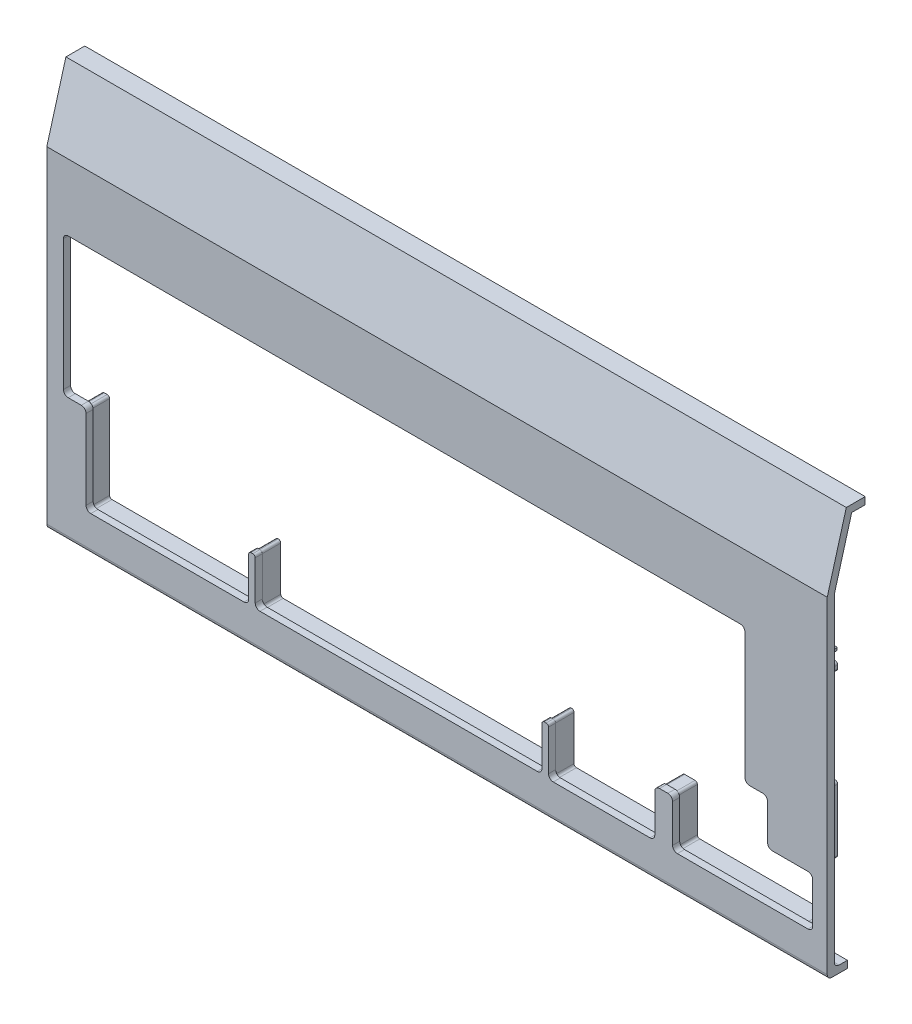
SolidWorks part; units mm, degrees
material "PET"
ref_plane "Front Plane" through (0, 0, 0) normal (0, 0, 1) x (1, 0, 0)
ref_plane "Top Plane" through (0, 0, 0) normal (0, 1, 0) x (1, 0, 0)
ref_plane "Right Plane" through (0, 0, 0) normal (1, 0, 0) x (0, 0, -1)
sketch "topprofile" plane through (853.0071, 0, 0) normal (1, 0, 0) x (0, 0, -1)
  line L0 (-0.0086, 1025.776) -> (-7.9776, 1025.776)
  line L2 (-16.0411, 996.9805) -> (-16.0411, 864.9805)
  line L8 (-13.0411, 864.9805) -> (-13.0411, 996.5684)
  line L10 (-5.7023, 1022.776) -> (-0.0086, 1022.776)
  line L11 (-0.0086, 1022.776) -> (-0.0086, 1025.776)
  line L13 (-16.0411, 996.9805) -> (-7.9776, 1025.776)
  line L15 (-5.7023, 1022.776) -> (-13.0411, 996.5684)
  line L16 (-13.0411, 864.9805) -> (-13.0411, 861.9953)
  line L17 (-11.0411, 859.9953) -> (-7.5187, 859.9953)
  line L18 (-16.0411, 864.9805) -> (-16.0411, 858.9953)
  line L19 (-14.0411, 856.9953) -> (-7.5187, 856.9953)
  line L20 (-7.5187, 859.9953) -> (-7.5187, 856.9953)
  arc A5 (-11.0411, 859.9953) -> (-13.0411, 861.9953) centre (-11.0411, 861.9953) cw
  arc A6 (-14.0411, 856.9953) -> (-16.0411, 858.9953) centre (-14.0411, 858.9953) cw
  dimension "D1" = 3
  dimension "D2" = 3
  dimension "D4" = 3
  dimension "D7" = 2
  dimension "D3" = 3
  dimension "D5" = 28.7954
  dimension "D6" = 132
extrude "faceplate" add sketch "topprofile" against normal up to surface (329.5 mm away)
sketch "keyboardcutout" plane through (0, 0, 16.0411) normal (0, 0, 1) x (1, 0, 0)
  line L0 (533.6471, 967.3544) -> (518.4377, 967.3544) construction
  line L1 (818.2971, 966.8544) -> (818.2971, 913.7044)
  line L2 (532.0471, 965.7544) -> (532.0471, 1029.3742) construction
  line L3 (530.5471, 966.8544) -> (530.5471, 911.7042)
  line L4 (532.5471, 968.8544) -> (816.2971, 968.8544)
  line L5 (816.7971, 965.7544) -> (816.7971, 984.5183) construction
  line L6 (824.7221, 910.2044) -> (842.7277, 910.2044) construction
  line L7 (826.3221, 908.6044) -> (826.3221, 926.0593) construction
  line L8 (843.7721, 891.1544) -> (863.4102, 891.1544) construction
  line L9 (820.2971, 911.7044) -> (825.8221, 911.7044)
  line L10 (827.8221, 909.7044) -> (827.8221, 894.6544)
  line L11 (829.8221, 892.6544) -> (844.8721, 892.6544)
  line L12 (845.3721, 889.5544) -> (845.3721, 899.3124) construction
  line L13 (846.8721, 890.6544) -> (846.8721, 873.6044)
  line L14 (843.7721, 873.1044) -> (861.095, 873.1044) construction
  line L15 (778.1971, 871.6044) -> (737.3346, 871.6044)
  line L16 (541.5721, 874.7044) -> (541.5721, 863.5167) construction
  line L17 (540.0721, 907.7042) -> (540.0721, 874.1044)
  line L18 (533.6471, 911.2042) -> (518.4377, 911.2042) construction
  line L19 (532.5471, 909.7042) -> (538.0721, 909.7042)
  line L20 (778.6971, 874.7044) -> (778.6971, 855.2363) construction
  line L21 (789.2221, 874.7044) -> (789.2221, 854.6734) construction
  line L22 (780.1971, 889.6544) -> (780.1971, 873.6044)
  line L23 (787.7221, 889.6544) -> (787.7221, 873.6044)
  line L24 (782.1971, 891.6544) -> (785.7221, 891.6544)
  line L25 (844.8721, 871.6044) -> (789.7221, 871.6044)
  line L26 (734.3346, 891.6544) -> (733.5721, 891.6544)
  line L27 (732.5721, 890.6544) -> (732.5721, 874.1044)
  line L28 (735.3346, 890.6544) -> (735.3346, 873.6044)
  line L29 (731.0721, 874.7044) -> (731.0721, 860.4434) construction
  line L30 (736.8346, 874.7044) -> (736.8346, 860.8815) construction
  line L31 (606.7471, 872.1044) -> (542.0721, 872.1044)
  line L32 (607.2471, 874.7044) -> (607.2471, 868.5767) construction
  line L33 (609.7471, 891.6544) -> (610.5096, 891.6544)
  line L34 (608.7471, 890.6544) -> (608.7471, 874.1044)
  line L36 (611.5096, 890.6544) -> (611.5096, 874.1044)
  line L37 (613.0096, 874.7044) -> (613.0096, 868.2785) construction
  line L38 (730.5721, 872.1044) -> (613.5096, 872.1044)
  arc A0 (530.5471, 911.7042) -> (532.5471, 909.7042) centre (532.5471, 911.7042) ccw
  arc A1 (540.0721, 907.7042) -> (538.0721, 909.7042) centre (538.0721, 907.7042) ccw
  arc A2 (540.0721, 874.1044) -> (542.0721, 872.1044) centre (542.0721, 874.1044) ccw
  arc A3 (606.7471, 872.1044) -> (608.7471, 874.1044) centre (606.7471, 874.1044) ccw
  arc A4 (613.5096, 872.1044) -> (611.5096, 874.1044) centre (613.5096, 874.1044) cw
  arc A5 (730.5721, 872.1044) -> (732.5721, 874.1044) centre (730.5721, 874.1044) ccw
  arc A6 (735.3346, 873.6044) -> (737.3346, 871.6044) centre (737.3346, 873.6044) ccw
  arc A7 (778.1971, 871.6044) -> (780.1971, 873.6044) centre (778.1971, 873.6044) ccw
  arc A8 (780.1971, 889.6544) -> (782.1971, 891.6544) centre (782.1971, 889.6544) cw
  arc A9 (785.7221, 891.6544) -> (787.7221, 889.6544) centre (785.7221, 889.6544) cw
  arc A10 (787.7221, 873.6044) -> (789.7221, 871.6044) centre (789.7221, 873.6044) ccw
  arc A11 (844.8721, 871.6044) -> (846.8721, 873.6044) centre (844.8721, 873.6044) ccw
  arc A12 (846.8721, 890.6544) -> (844.8721, 892.6544) centre (844.8721, 890.6544) ccw
  arc A13 (829.8221, 892.6544) -> (827.8221, 894.6544) centre (829.8221, 894.6544) cw
  arc A14 (825.8221, 911.7044) -> (827.8221, 909.7044) centre (825.8221, 909.7044) cw
  arc A15 (820.2971, 911.7044) -> (818.2971, 913.7044) centre (820.2971, 913.7044) cw
  arc A16 (818.2971, 966.8544) -> (816.2971, 968.8544) centre (816.2971, 966.8544) ccw
  arc A17 (530.5471, 966.8544) -> (532.5471, 968.8544) centre (532.5471, 966.8544) cw
  arc A18 (732.5721, 890.6544) -> (733.5721, 891.6544) centre (733.5721, 890.6544) cw
  arc A19 (735.3346, 890.6544) -> (734.3346, 891.6544) centre (734.3346, 890.6544) ccw
  arc A20 (611.5096, 890.6544) -> (610.5096, 891.6544) centre (610.5096, 890.6544) ccw
  arc A21 (608.7471, 890.6544) -> (609.7471, 891.6544) centre (609.7471, 890.6544) cw
  point P63 (608.7471, 872.1044)
  point P72 (780.1971, 871.6044)
  point P75 (780.1971, 891.6544)
  dimension "D20" = 2
  dimension "D21" = 1
  dimension "D1" = 1.5
  dimension "D2" = 1.5
  dimension "D3" = 1.5
  dimension "D4" = 1.5
  dimension "D5" = 1.5
  dimension "D6" = 1.5
  dimension "D7" = 1.5
  dimension "D8" = 1
  dimension "D9" = 1.5
  dimension "D10" = 1.5
  dimension "D11" = 1.5
  dimension "D12" = 1.5
  dimension "D13" = 1.5
  dimension "D14" = 1.5
  dimension "D15" = 1.5
  dimension "D16" = 1
  dimension "D17" = 0
  dimension "D18" = 1.5
  dimension "D19" = 1.5
extrude "keyboardhole" cut sketch "keyboardcutout" against normal up to next
sketch "Sketch1" plane through (0, 0, 13.0411) normal (0, 0, -1) x (-1, 0, 0)
  line L0 (-779.7829, 870.6563) -> (-736.0417, 870.6563)
  line L1 (-786.1364, 891.0686) -> (-781.7829, 891.0686)
  line L2 (-787.1364, 890.0686) -> (-787.1364, 871.6563)
  line L4 (-780.7829, 890.0686) -> (-780.7829, 871.6563)
  line L5 (-734.0417, 891.3615) -> (-733.865, 891.3615)
  line L6 (-735.0417, 890.3615) -> (-735.0417, 871.6563)
  line L8 (-732.865, 890.3615) -> (-732.865, 871.6563)
  line L9 (-610.2167, 891.3615) -> (-610.04, 891.3615)
  line L10 (-611.2167, 890.3615) -> (-611.2167, 871.6563)
  line L12 (-609.04, 890.3615) -> (-609.04, 874.7537)
  line L17 (-841.2114, 870.6563) -> (-788.1364, 870.6563)
  line L18 (-842.2114, 869.6563) -> (-842.2114, 868.214)
  line L19 (-841.2114, 867.214) -> (-536.7493, 867.214)
  line L20 (-535.7493, 870.6563) -> (-535.7493, 868.214)
  line L25 (-537.9629, 908.0689) -> (-536.7493, 908.0689)
  line L26 (-538.9629, 907.0689) -> (-538.9629, 874.7537)
  line L28 (-535.7493, 907.0689) -> (-535.7493, 870.6563)
  line L29 (-819.8829, 912.2902) -> (-820.0121, 912.2902)
  line L30 (-818.8829, 913.2902) -> (-818.8829, 935.1679)
  line L31 (-819.8829, 936.1679) -> (-820.0121, 936.1679)
  line L32 (-821.0121, 913.2902) -> (-821.0121, 935.1679)
  line L33 (-829.4079, 893.2402) -> (-829.4496, 893.2402)
  line L34 (-828.4079, 894.2402) -> (-828.4079, 909.5208)
  line L35 (-829.4079, 910.5208) -> (-829.4496, 910.5208)
  line L36 (-830.4496, 894.2402) -> (-830.4496, 909.5208)
  line L37 (-845.371, 920.8228) -> (-844.7054, 920.8228)
  line L38 (-846.371, 919.8228) -> (-846.371, 893.7984)
  line L39 (-845.371, 892.7984) -> (-844.7054, 892.7984)
  line L40 (-843.7054, 919.8228) -> (-843.7054, 893.7984)
  line L41 (-839.5356, 925.9379) -> (-825.326, 925.9379)
  line L42 (-840.5356, 924.9379) -> (-840.5356, 924.2723)
  line L43 (-839.5356, 923.2723) -> (-825.326, 923.2723)
  line L44 (-824.326, 924.9379) -> (-824.326, 924.2723)
  line L45 (-834.7111, 964.4697) -> (-845.371, 964.4697)
  line L46 (-833.7111, 963.4697) -> (-833.7111, 962.0185)
  line L47 (-834.7111, 961.0185) -> (-845.371, 961.0185)
  line L48 (-846.371, 963.4697) -> (-846.371, 962.0185)
  line L49 (-529.3779, 969.7515) -> (-846.1606, 969.7515)
  line L51 (-529.3779, 968.5685) -> (-846.1606, 968.5685)
  line L53 (-731.865, 870.6563) -> (-612.2167, 870.6563)
  line L54 (-608.04, 870.6563) -> (-539.9629, 870.6563)
  line L55 (-538.9629, 871.6563) -> (-538.9629, 874.7537)
  line L56 (-609.04, 874.7537) -> (-609.04, 871.6563)
  line L57 (-846.1606, 969.7515) -> (-846.1606, 968.5685)
  line L58 (-529.3779, 969.7515) -> (-529.3779, 968.5685)
  arc A0 (-820.2971, 911.7044) -> (-818.2971, 913.7044) centre (-820.2971, 913.7044) ccw construction
  arc A1 (-780.1971, 889.6544) -> (-782.1971, 891.6544) centre (-782.1971, 889.6544) ccw construction
  arc A2 (-785.7221, 891.6544) -> (-787.7221, 889.6544) centre (-785.7221, 889.6544) ccw construction
  arc A3 (-734.3346, 891.6544) -> (-735.3346, 890.6544) centre (-734.3346, 890.6544) ccw construction
  arc A4 (-732.5721, 890.6544) -> (-733.5721, 891.6544) centre (-733.5721, 890.6544) ccw construction
  arc A5 (-610.5096, 891.6544) -> (-611.5096, 890.6544) centre (-610.5096, 890.6544) ccw construction
  arc A6 (-608.7471, 890.6544) -> (-609.7471, 891.6544) centre (-609.7471, 890.6544) ccw construction
  arc A7 (-609.04, 890.3615) -> (-610.04, 891.3615) centre (-610.04, 890.3615) ccw
  arc A8 (-611.2167, 890.3615) -> (-610.2167, 891.3615) centre (-610.2167, 890.3615) cw
  arc A9 (-732.865, 890.3615) -> (-733.865, 891.3615) centre (-733.865, 890.3615) ccw
  arc A10 (-735.0417, 890.3615) -> (-734.0417, 891.3615) centre (-734.0417, 890.3615) cw
  arc A11 (-780.7829, 890.0686) -> (-781.7829, 891.0686) centre (-781.7829, 890.0686) ccw
  arc A12 (-787.1364, 890.0686) -> (-786.1364, 891.0686) centre (-786.1364, 890.0686) cw
  arc A13 (-829.8221, 892.6544) -> (-827.8221, 894.6544) centre (-829.8221, 894.6544) ccw construction
  arc A14 (-829.4079, 893.2402) -> (-828.4079, 894.2402) centre (-829.4079, 894.2402) ccw
  arc A15 (-818.8829, 913.2902) -> (-819.8829, 912.2902) centre (-819.8829, 913.2902) cw
  arc A20 (-833.7111, 963.4697) -> (-834.7111, 964.4697) centre (-834.7111, 963.4697) ccw
  arc A21 (-833.7111, 962.0185) -> (-834.7111, 961.0185) centre (-834.7111, 962.0185) cw
  arc A22 (-845.371, 961.0185) -> (-846.371, 962.0185) centre (-845.371, 962.0185) cw
  arc A23 (-846.371, 963.4697) -> (-845.371, 964.4697) centre (-845.371, 963.4697) cw
  arc A24 (-820.0121, 936.1679) -> (-821.0121, 935.1679) centre (-820.0121, 935.1679) ccw
  arc A25 (-819.8829, 936.1679) -> (-818.8829, 935.1679) centre (-819.8829, 935.1679) cw
  arc A26 (-824.326, 924.9379) -> (-825.326, 925.9379) centre (-825.326, 924.9379) ccw
  arc A27 (-824.326, 924.2723) -> (-825.326, 923.2723) centre (-825.326, 924.2723) cw
  arc A28 (-840.5356, 924.2723) -> (-839.5356, 923.2723) centre (-839.5356, 924.2723) ccw
  arc A29 (-840.5356, 924.9379) -> (-839.5356, 925.9379) centre (-839.5356, 924.9379) cw
  arc A30 (-846.371, 919.8228) -> (-845.371, 920.8228) centre (-845.371, 919.8228) cw
  arc A31 (-844.7054, 920.8228) -> (-843.7054, 919.8228) centre (-844.7054, 919.8228) cw
  arc A32 (-821.0121, 913.2902) -> (-820.0121, 912.2902) centre (-820.0121, 913.2902) ccw
  arc A33 (-828.4079, 909.5208) -> (-829.4079, 910.5208) centre (-829.4079, 909.5208) ccw
  arc A34 (-830.4496, 909.5208) -> (-829.4496, 910.5208) centre (-829.4496, 909.5208) cw
  arc A35 (-830.4496, 894.2402) -> (-829.4496, 893.2402) centre (-829.4496, 894.2402) ccw
  arc A36 (-845.371, 892.7984) -> (-846.371, 893.7984) centre (-845.371, 893.7984) cw
  arc A37 (-843.7054, 893.7984) -> (-844.7054, 892.7984) centre (-844.7054, 893.7984) cw
  arc A38 (-841.2114, 867.214) -> (-842.2114, 868.214) centre (-841.2114, 868.214) cw
  arc A39 (-842.2114, 869.6563) -> (-841.2114, 870.6563) centre (-841.2114, 869.6563) cw
  arc A40 (-538.9629, 907.0689) -> (-537.9629, 908.0689) centre (-537.9629, 907.0689) cw
  arc A41 (-535.7493, 907.0689) -> (-536.7493, 908.0689) centre (-536.7493, 907.0689) ccw
  arc A42 (-536.7493, 867.214) -> (-535.7493, 868.214) centre (-536.7493, 868.214) ccw
  arc A43 (-539.9629, 870.6563) -> (-538.9629, 871.6563) centre (-539.9629, 871.6563) ccw
  arc A44 (-608.04, 870.6563) -> (-609.04, 871.6563) centre (-608.04, 871.6563) cw
  arc A45 (-612.2167, 870.6563) -> (-611.2167, 871.6563) centre (-612.2167, 871.6563) ccw
  arc A46 (-731.865, 870.6563) -> (-732.865, 871.6563) centre (-731.865, 871.6563) cw
  arc A47 (-736.0417, 870.6563) -> (-735.0417, 871.6563) centre (-736.0417, 871.6563) ccw
  arc A48 (-779.7829, 870.6563) -> (-780.7829, 871.6563) centre (-779.7829, 871.6563) cw
  arc A49 (-788.1364, 870.6563) -> (-787.1364, 871.6563) centre (-788.1364, 871.6563) ccw
  point P34 (-609.04, 891.3615)
  point P37 (-611.2167, 891.3615)
  point P40 (-732.865, 891.3615)
  point P43 (-735.0417, 891.3615)
  point P46 (-780.7829, 891.0686)
  point P49 (-787.1364, 891.0686)
  point P84 (-828.4079, 893.2402)
  point P87 (-818.8829, 912.2902)
  point P161 (-787.1364, 870.6563)
  dimension "D1" = 1
  dimension "D2" = 1
extrude "pcbstandoff" add sketch "Sketch1" along normal up to surface (8.0624 mm away)
